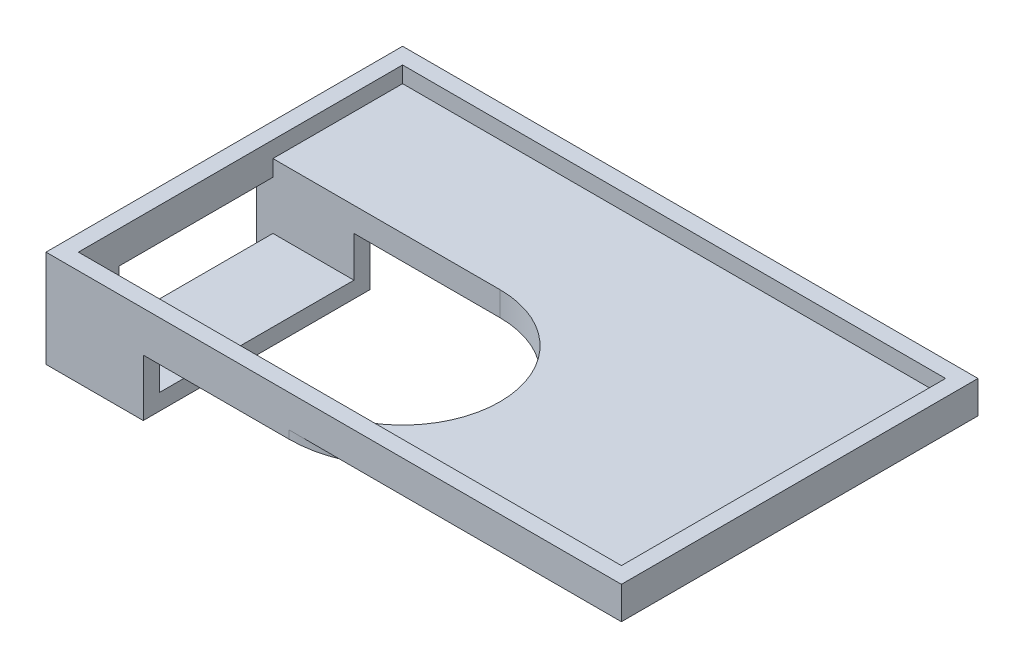
SolidWorks part; units mm, degrees
ref_plane "Front Plane" through (0, 0, 0) normal (0, 0, 1) x (1, 0, 0)
ref_plane "Top Plane" through (0, 0, 0) normal (0, 1, 0) x (1, 0, 0)
ref_plane "Right Plane" through (0, 0, 0) normal (1, 0, 0) x (0, 0, -1)
sketch "Sketch1" plane through (0, 0, 0) normal (0, 1, 0) x (1, 0, 0)
  line L0 (0, -16) -> (28, -16)
  line L1 (0, 0) -> (67, 0)
  line L2 (0, 0) -> (0, -40)
  line L3 (0, -40) -> (67, -40)
  line L4 (67, 0) -> (67, -40)
  line L5 (28, -16) -> (28, -40) construction
  line L6 (-2, 2) -> (69, 2)
  line L7 (69, 2) -> (69, -42)
  line L8 (-2, -42) -> (69, -42)
  line L9 (-2, 2) -> (-2, -42)
  arc A0 (28, -16) -> (28, -40) centre (28, -28) cw
  point P14 (28, -18.3635)
  dimension "D1" = 67
  dimension "D2" = 40
  dimension "D3" = 24
  dimension "D4" = 28
  dimension "D5" = 2
extrude "Boss-Extrude1" add sketch "Sketch1" along normal blind 2 contours L2 L1 L4 L3
extrude "Boss-Extrude2" add sketch "Sketch1<3>" along normal blind 4 contours L6 L9 L8 L7 L1 L4 L3 L2 region at (33.5, 0, -1.1647)
sketch "Sketch1<3>" plane through (0, 0, 0) normal (0, 1, 0) x (1, 0, 0) same geometry as "Sketch1"
extrude "Cut-Extrude4" cut sketch "Sketch1<5>" along normal up to surface (2 mm away) contours L5 L0 L2 L3 | A0 L5 region at (14, 0, 28) region at (33.093, 0, 28) up to face at (33.5, 2, 20)
sketch "Sketch1<5>" plane through (0, 0, 0) normal (0, 1, 0) x (1, 0, 0) same geometry as "Sketch1"
sketch "Sketch2" plane through (0, 0, 0) normal (0, -1, 0) x (1, 0, 0)
  line L10 (0, 16) -> (28, 16) construction
  line L11 (10, 16) -> (-2, 16)
  line L12 (10, 16) -> (10, 14)
  line L13 (10, 14) -> (-2, 14)
  line L14 (-2, 16) -> (-2, 14)
  line L15 (-2, -2) -> (-2, 42) construction
  line L17 (0, 40) -> (28, 40) construction
  line L18 (-2, 42) -> (10, 42)
  line L19 (-2, 42) -> (-2, 40)
  line L20 (0, 40) -> (10, 40)
  line L21 (10, 42) -> (10, 40)
  line L22 (0, 16) -> (0, 40) construction
  line L24 (-2, 40) -> (-2, 35)
  line L25 (-2, 35) -> (0, 35)
  line L26 (0, 40) -> (0, 35)
  dimension "D1" = 12
  dimension "D2" = 5
  dimension "D3" = 2
extrude "Boss-Extrude3" add sketch "Sketch2" along normal blind 8
sketch "Sketch3" plane through (0, 0, 40) normal (0, 0, -1) x (-1, 0, 0)
  line L0 (0, 4) -> (0, -8) construction
  line L1 (-10, -8) -> (0, -8)
  line L2 (-10, -8) -> (-10, -6)
  line L3 (-10, -6) -> (0, -6)
  line L4 (0, -8) -> (0, -6)
  dimension "D1" = 2
extrude "Boss-Extrude4" add sketch "Sketch3" along normal blind 24
sketch "Sketch4" plane through (0, 0, 0) normal (1, 0, 0) x (0, 0, -1)
  line L1 (-16, 0) -> (-22, 0)
  line L2 (-16, 0) -> (-16, 2)
  line L3 (-16, 2) -> (-22, 2)
  line L4 (-22, 0) -> (-22, 2)
  dimension "D1" = 6
  dimension "D2" = 2
sketch "Sketch5" plane through (0, 0, 0) normal (0, -1, 0) x (1, 0, 0)
  line L0 (10, 16) -> (28, 16) construction
  line L1 (10, 40) -> (28, 40) construction
  line L2 (10, 16) -> (28, 16)
  line L3 (10, 40) -> (28, 40)
  line L4 (10, 42) -> (28, 42)
  line L5 (10, 14) -> (28, 14)
  line L6 (10, 40) -> (10, 42)
  line L7 (10, 14) -> (10, 16)
  arc A0 (28, 16) -> (28, 40) centre (28, 28) ccw construction
  arc A1 (28, 16) -> (28, 40) centre (28, 28) ccw
  arc A2 (28, 14) -> (28, 42) centre (28, 28) ccw
  dimension "D1" = 2
extrude "Boss-Extrude5" add sketch "Sketch5" along normal blind 1
